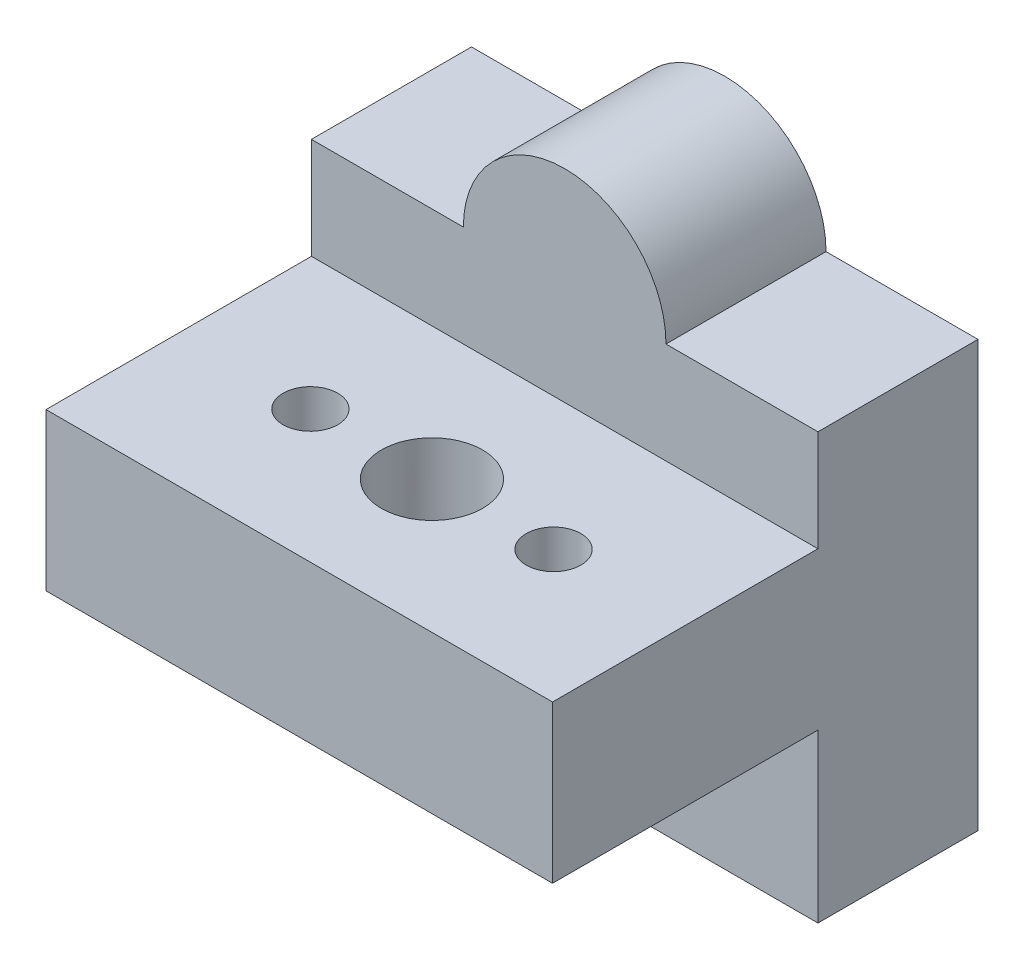
SolidWorks part; units mm, degrees
note: The reader was unsure of these and kept them because the rebuilt part matched: shared geometry of "Sketch2<4>", "Sketch2<6>".
ref_plane "Front Plane" through (0, 0, 0) normal (0, 0, 1) x (1, 0, 0)
ref_plane "Top Plane" through (0, 0, 0) normal (0, 1, 0) x (1, 0, 0)
ref_plane "Right Plane" through (0, 0, 0) normal (1, 0, 0) x (0, 0, -1)
sketch "Sketch1" plane through (0, 0, 0) normal (0, 0, 1) x (1, 0, 0)
  line L0 (-5, 10.5) -> (-12.5, 10.5)
  line L1 (12.5, -10.5) -> (-12.5, -10.5)
  line L2 (12.5, -10.5) -> (12.5, 10.5)
  line L3 (12.5, 10.5) -> (5, 10.5)
  line L4 (-12.5, -10.5) -> (-12.5, 10.5)
  line L5 (12.5, -10.5) -> (-12.5, 10.5) construction
  line L6 (12.5, 10.5) -> (-12.5, -10.5) construction
  arc A0 (5, 10.5) -> (-5, 10.5) centre (0, 10.5) ccw
  point P0 (0, 0)
  dimension "D3" = 10
  dimension "D1" = 21
  dimension "D2" = 25
extrude "Boss-Extrude1" add sketch "Sketch1" along normal blind 7.9
ref_plane "Plane1" through (0, -2.25, 0) normal (0, -1, 0) x (-1, 0, 0)
sketch "Sketch2" plane through (0, -2.25, 0) normal (0, 1, 0) x (1, 0, 0)
  line L1 (12.5, -7.9) -> (-12.5, -7.9)
  line L2 (12.5, -7.9) -> (12.5, -21)
  line L3 (12.5, -21) -> (-12.5, -21)
  line L4 (-12.5, -7.9) -> (-12.5, -21)
  line L5 (12.5, -7.9) -> (-12.5, -21) construction
  line L6 (12.5, -21) -> (-12.5, -7.9) construction
  circle A0 centre (0, -14.45) radius 2.5
  circle A1 centre (-6.0001, -14.45) radius 2.6999
  circle A2 centre (6.0002, -14.45) radius 2.6999
  circle A3 centre (-6.0001, -14.45) radius 1.3498
  circle A4 centre (6.0002, -14.45) radius 1.3498
  point P4 (0, -14.45)
  dimension "D2" = 5
  dimension "D3" = 5.3999
  dimension "D6" = 2.6997
  dimension "D7" = 2.6997
  dimension "D1" = 13.1
  dimension "D4" = 6.0002
  dimension "D5" = 6.0002
extrude "Boss-Extrude2" add sketch "Sketch2" along normal blind 7.75 contours A2 A4 | A1 A3 | L2 L1 L4 L3
extrude "Cut-Extrude1" cut sketch "Sketch2<4>" along normal blind 23.498 contours A3 | A0
sketch "Sketch2<4>" plane through (0, -2.25, 0) normal (0, 1, 0) x (1, 0, 0) same geometry as "Sketch2"
extrude "Cut-Extrude2" cut sketch "Sketch2<6>" along normal blind 2.5 contours A2 A4 | A1 A3
sketch "Sketch2<6>" plane through (0, -2.25, 0) normal (0, 1, 0) x (1, 0, 0) same geometry as "Sketch2"
